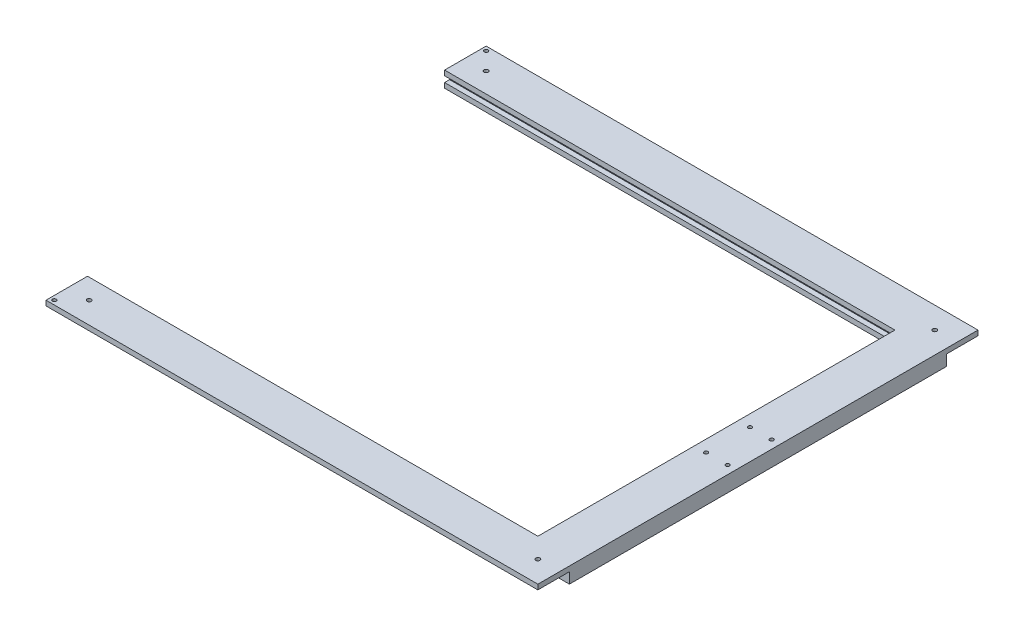
SolidWorks part; units mm, degrees
ref_plane "Спереди" through (0, 0, 0) normal (0, 0, 1) x (1, 0, 0)
ref_plane "Сверху" through (0, 0, 0) normal (0, 1, 0) x (1, 0, 0)
ref_plane "Справа" through (0, 0, 0) normal (1, 0, 0) x (0, 0, -1)
sketch "Эскиз1" plane through (0, 0, 0) normal (0, 1, 0) x (1, 0, 0)
  line L0 (50, -77.9215) -> (50, -607.9215)
  line L1 (-542.3, -77.9215) -> (50, -77.9215)
  line L2 (-542.3, -77.9215) -> (-542.3, -127.9215)
  line L3 (-542.3, -607.9215) -> (50, -607.9215)
  line L5 (-542.3, -127.9215) -> (0, -127.9215)
  line L7 (-542.3, -557.9215) -> (0, -557.9215)
  line L13 (-542.3, -557.9215) -> (-542.3, -607.9215)
  line L22 (0, -127.9215) -> (0, -557.9215)
  dimension "D1" = 592.3
  dimension "D12" = 50
  dimension "D2" = 530
  dimension "D3" = 50
  dimension "D4" = 50
  dimension "D9" = 50
  dimension "D8" = 77.9215
extrude "Бобышка-Вытянуть2" add sketch "Эскиз1" along normal blind 6
sketch "Эскиз2" plane through (0, 0, 0) normal (0, -1, 0) x (1, 0, 0)
  line L0 (-542.3, 127.9215) -> (0, 127.9215) construction
  line L5 (50, 607.9215) -> (50, 77.9215) construction
  line L6 (0, 557.9215) -> (-542.3, 557.9215) construction
  line L18 (50, 569.9215) -> (50, 115.9215)
  line L20 (6, 563.9215) -> (6, 121.9215)
  line L21 (-542.3, 77.9215) -> (-542.3, 127.9215) construction
  line L22 (50, 115.9215) -> (-542.3, 115.9215)
  line L24 (6, 121.9215) -> (-542.3, 121.9215)
  line L25 (-542.3, 115.9215) -> (-542.3, 121.9215)
  line L26 (-542.3, 557.9215) -> (-542.3, 607.9215) construction
  line L27 (50, 569.9215) -> (-542.3, 569.9215)
  line L29 (6, 563.9215) -> (-542.3, 563.9215)
  line L30 (-542.3, 569.9215) -> (-542.3, 563.9215)
  dimension "D1" = 44
  dimension "D2" = 6
  dimension "D3" = 6
  dimension "D4" = 6
  dimension "D5" = 6
extrude "Бобышка-Вытянуть3" add sketch "Эскиз2" along normal blind 7
sketch "Эскиз4" plane through (0, 6, 0) normal (0, 1, 0) x (1, 0, 0)
  line L0 (50, -77.9215) -> (-542.3, -77.9215) construction
  line L1 (-542.3, -77.9215) -> (-542.3, -127.9215) construction
  circle A0 centre (-516.3, -103.9215) radius 2.5
  dimension "D1" = 5
  dimension "D2" = 26
  dimension "D3" = 26
extrude "Вырез-Вытянуть1" cut sketch "Эскиз4" against normal through all
pattern_linear "Линейный массив2" count 2 spacing 540.3 along (1, 0, 0) count 2 spacing 478 along (0, 0, 1) of "Вырез-Вытянуть1"
sketch "Эскиз5" plane through (0, -7, 0) normal (0, -1, 0) x (1, 0, 0)
  line L8 (50, 569.9215) -> (-542.3, 569.9215)
  line L9 (-542.3, 569.9215) -> (-542.3, 557.9215)
  line L10 (-542.3, 557.9215) -> (0, 557.9215)
  line L11 (0, 557.9215) -> (0, 127.9215)
  line L12 (0, 127.9215) -> (-542.3, 127.9215)
  line L13 (-542.3, 127.9215) -> (-542.3, 115.9215)
  line L14 (-542.3, 115.9215) -> (50, 115.9215)
  line L15 (50, 115.9215) -> (50, 569.9215)
extrude "Бобышка-Вытянуть4" add sketch "Эскиз5" along normal blind 6
sketch "Эскиз6" plane through (0, -13, 0) normal (0, -1, 0) x (1, 0, 0)
  line L0 (40, 342.9215) -> (50, 342.9215) construction
  line L1 (40, 316.4215) -> (14, 316.4215) construction
  line L2 (40, 316.4215) -> (40, 369.4215) construction
  line L3 (40, 369.4215) -> (14, 369.4215) construction
  line L4 (14, 316.4215) -> (14, 369.4215) construction
  line L5 (50, 115.9215) -> (50, 569.9215) construction
  circle A1 centre (14, 369.4215) radius 2.25
  circle A2 centre (40, 369.4215) radius 2.25
  circle A3 centre (40, 316.4215) radius 2.25
  circle A4 centre (14, 316.4215) radius 2.25
  point P4 (50, 342.9215)
  point P6 (40, 342.9215)
  dimension "D4" = 4.5
  dimension "D1" = 53
  dimension "D2" = 26
  dimension "D3" = 10
extrude "Вырез-Вытянуть2" cut sketch "Эскиз6" against normal through all
sketch "Эскиз7" plane through (0, 0, 0) normal (0, -1, 0) x (1, 0, 0)
  line L0 (-542.3, 597.9215) -> (-532.3, 607.9215) construction
  line L1 (-542.3, 607.9215) -> (-532.3, 607.9215) construction
  line L2 (-542.3, 607.9215) -> (-542.3, 597.9215) construction
  line L3 (-542.3, 597.9215) -> (-532.3, 597.9215) construction
  line L4 (-532.3, 607.9215) -> (-532.3, 597.9215) construction
  line L5 (-542.3, 607.9215) -> (-532.3, 597.9215) construction
  line L6 (-532.3, 87.9215) -> (-542.3, 77.9215) construction
  line L7 (-542.3, 77.9215) -> (-532.3, 77.9215) construction
  line L8 (-542.3, 77.9215) -> (-542.3, 87.9215) construction
  line L9 (-542.3, 87.9215) -> (-532.3, 87.9215) construction
  line L10 (-532.3, 77.9215) -> (-532.3, 87.9215) construction
  line L11 (-542.3, 87.9215) -> (-532.3, 77.9215) construction
  circle A0 centre (-537.3, 602.9215) radius 2.25
  circle A1 centre (-537.3, 82.9215) radius 2.25
  point P12 (-537.3, 82.9215)
  dimension "D3" = 4.5
  dimension "D6" = 4.5
  dimension "D1" = 10
  dimension "D2" = 10
  dimension "D4" = 10
  dimension "D5" = 10
extrude "Вырез-Вытянуть3" cut sketch "Эскиз7" against normal through all
equation "\"Ширина груза\"= 420"
equation "\"Глубина груза\"= 490"
equation "\"Высота груза\"= 297"
equation "\"Ширина ячейки\"= \"Ширина груза\" + 10"
equation "\"Глубина ячейки\"= \"Глубина груза\" + 10"
equation "\"Высота ячейки\"= \"Высота груза\" + 10 + 13"
equation "\"Колво ячеек ширина\"= 2"
equation "\"Колво ячеек высота\"= 2"
equation "\"Толщина стенки\" = 6"
equation "\"Крепление дверцы\"= 5 "
equation "\"Ширина рейки\"= \"Толщина шестерни\""
equation "\"Высота рейки\"= 20"
equation "\"Высота пола\"= \"Толщина стенки\" * 2"
equation "\"Колво полозьев\"= 5"
equation "\"Отступ рейки\"= 20"
equation "\"Глубина каретки\"= \"Глубина ячейки\" + 30 + \"Мотор Y высота корпуса\" + 20"
equation "\"Длинна рейки\" = (\"Ширина ячейки\" + \"Толщина стенки\" + \"Крепление дверцы\") * \"Колво ячеек ширина\" + \"Ширина ячейки выгрузки\" * \"Колво выгрузки\" + \"Толщина стенки\" + \"Отступ крепления мотора фиксации\" * 2 - \"Крепление дверцы\" * \"Колво ячеек ширина\""
equation "\"Отступ шпильки\"= 26"
equation "\"Диаметр шпильки\"= 5"
equation "\"Длинна шпильки\"= ( \"Высота ячейки\" + \"Толщина стенки\" + \"Высота пола\" ) * \"Колво ячеек высота\" + ( \"Толщина стенки\" + \"Отступ рейки\" ) * 2 "
equation "\"D2@Эскиз1\"=\"Ширина ячейки\" + \"Ширина пластины\" * 2 "
equation "\"D9@Эскиз1\"=\"Ширина пластины\""
equation "\"D3@Эскиз1\"=\"Ширина пластины\""
equation "\"D4@Эскиз1\"= \"Ширина пластины\""
equation "\"Ширина пластины\"= 50  "
equation "\"D1@Бобышка-Вытянуть2\"=\"Толщина стенки\""
equation "\"D1@Эскиз4\"= \"Диаметр шпильки\""
equation "\"D4@Линейный массив2\"=\"Ширина ячейки\" + \"Ширина пластины\" * 2  - \"Отступ шпильки\" * 2"
equation "\"D1@Эскиз1\"= \"Глубина каретки\""
equation "\"D3@Линейный массив2\"= \"Глубина каретки\" - \"Отступ шпильки\" * 2"
equation "\"D2@Эскиз4\"=\"Отступ шпильки\""
equation "\"D3@Эскиз4\"= \"Отступ шпильки\""
equation "\"D1@Эскиз2\"= \"Ширина пластины\" - \"Толщина стенки\""
equation "\"D2@Эскиз2\"= \"Толщина стенки\""
equation "\"D3@Эскиз2\"= \"Толщина стенки\""
equation "\"D4@Эскиз2\"= \"Толщина стенки\""
equation "\"D5@Эскиз2\"= \"Толщина стенки\""
equation "\"D1@Бобышка-Вытянуть4\"= \"Толщина стенки\""
equation "\"Вы\"=20"
equation "\"D1@Бобышка-Вытянуть3\"=\"Высота пола\" - 5"
equation "\"Высота зона выгрузки\"= \"Высота ячейки\" * 2 + \"Толщина стенки\" * 2"
equation "\"Колво выгрузки\"= 1"
equation "\"Ширина ячейки выгрузки\"= \"Ширина ячейки\" + \"Толщина стенки\" + \"Отступ крепления мотора фиксации\"*2"
equation "\"Отступ крепления мотора фиксации\" = (\"Ширина пластины\" + 20 - \"Толщина стенки\") / 2"
equation "\"Мотор X ширина корпуса\"= 42.3"
equation "\"Мотор X высота корпуса\"= 42.3"
equation "\"Мотор X длина корпуса\"= 40"
equation "\"Мотор X вылет вала\"= 19.8"
equation "\"Мотор Y ширина корпуса\"= 42.3"
equation "\"Мотор Y высота корпуса\"= 42.3"
equation "\"Мотор Y длина корпуса\"= 48"
equation "\"Мотор Y вылет вала\"= 30"
equation "\"Мотор Z ширина корпуса\"= 42"
equation "\"Мотор Z высота корпуса\"= 42"
equation "\"Мотор Z длина корпуса\"= 40"
equation "\"Мотор Z вылет вала\"= 23"
equation "\"Мотор диаметр вала ПРЕДВ\"= 5"
equation "\"Мотор шаг крепления ПРЕДВ\"= 31"
equation "\"Мотор диаметр отверстий ПРЕДВ\"= 3"
equation "\"Мотор глубина отверстий ПРЕДВ\"= 4.5"
equation "\"Мотор диаметр буртика ПРЕДВ\"= 22"
equation "\"Мотор высота буртика ПРЕДВ\"= 2"
equation "\"Мотор диаметр шкива ПРЕДВ\"= 16"
equation "\"Мотор длина шкива ПРЕДВ\"= 12"
equation "\"Мотор отступ шкива ПРЕДВ\"= 5"
equation "\"Мотор X шаг градусов\"= 1.8"
equation "\"Мотор X ток А\"= 1.5"
equation "\"Мотор X сопротивление Ом\"= 1.3"
equation "\"Мотор X индуктивность мГн\"= 2"
equation "\"Мотор Y шаг градусов\"= 1.8"
equation "\"Мотор Y ток А\"= 2.2"
equation "\"Мотор Y сопротивление Ом\"= 0.9"
equation "\"Мотор Y индуктивность мГн\"= 2"
equation "\"Мотор Z шаг градусов\"= 1.8"
equation "\"Мотор Z ток А\"= 1"
equation "\"Мотор Z сопротивление Ом\"= 4"
equation "\"Мотор Z индуктивность мГн\"= 8"
equation "\"Мотор Y диаметр ротора\"= 25.78"
